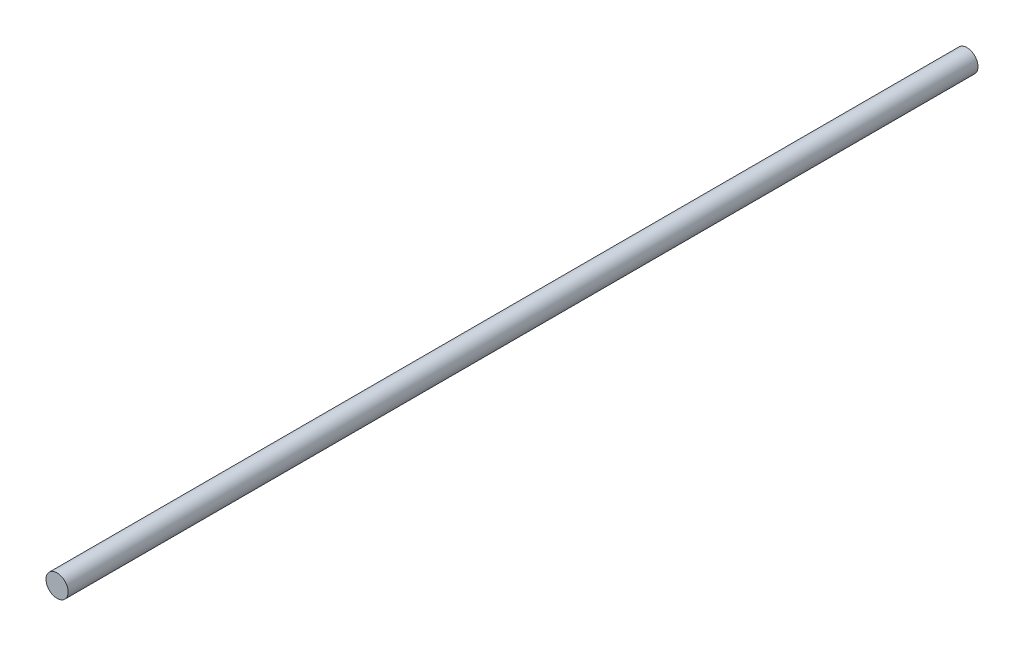
SolidWorks part; units mm, degrees
ref_plane "Front Plane" through (0, 0, 0) normal (0, 0, 1) x (1, 0, 0)
ref_plane "Top Plane" through (0, 0, 0) normal (0, 1, 0) x (1, 0, 0)
ref_plane "Right Plane" through (0, 0, 0) normal (1, 0, 0) x (0, 0, -1)
sketch "Sketch1" plane through (0, 0, 0) normal (0, 0, 1) x (1, 0, 0)
  circle A0 centre (0, 0) radius 6
  dimension "D1" = 12
extrude "Boss-Extrude1" add sketch "Sketch1" along normal mid plane 494
